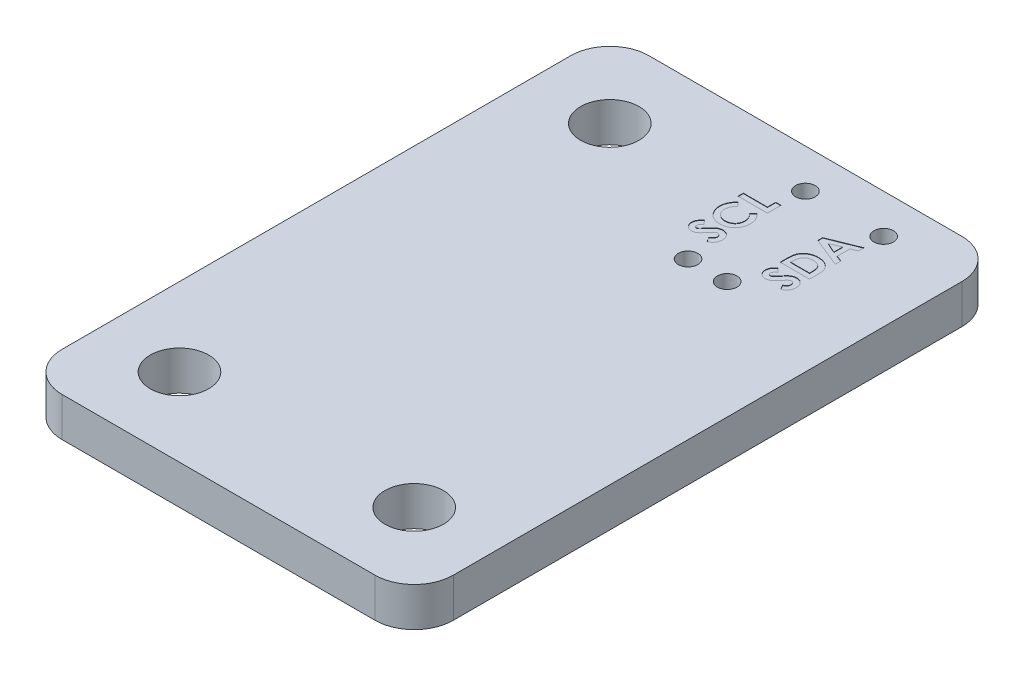
SolidWorks part; units mm, degrees
ref_plane "Front Plane" through (0, 0, 0) normal (0, 0, 1) x (1, 0, 0)
ref_plane "Top Plane" through (0, 0, 0) normal (0, 1, 0) x (1, 0, 0)
ref_plane "Right Plane" through (0, 0, 0) normal (1, 0, 0) x (0, 0, -1)
sketch "Sketch1" plane through (0, 0, 0) normal (0, 1, 0) x (1, 0, 0)
  line L1 (-12.7, -19.05) -> (12.7, -19.05)
  line L2 (-12.7, -19.05) -> (-12.7, 19.05)
  line L3 (-12.7, 19.05) -> (12.7, 19.05)
  line L4 (12.7, -19.05) -> (12.7, 19.05)
  line L5 (-12.7, -19.05) -> (12.7, 19.05) construction
  line L6 (-12.7, 19.05) -> (12.7, -19.05) construction
  point P0 (0, 0)
  dimension "D1" = 38.1
  dimension "D2" = 25.4
extrude "Boss-Extrude1" add sketch "Sketch1" along normal mid plane 2.54
fillet "Fillet1" radius 2.54 4 edges at (-12.7, 0, -19.05) (12.7, 0, -19.05) (-12.7, 0, 19.05) (12.7, 0, 19.05)
sketch "Sketch2" plane through (0, 1.27, 0) normal (0, 1, 0) x (1, 0, 0)
  line L0 (12.7, -16.51) -> (12.7, 16.51) construction
  line L1 (10.16, 19.05) -> (-10.16, 19.05) construction
  line L2 (2.54, 16.51) -> (2.54, 8.89) construction
  line L3 (7.62, 16.51) -> (7.62, 8.89) construction
  circle A0 centre (7.62, 16.51) radius 0.635
  circle A1 centre (2.54, 16.51) radius 0.635
  circle A2 centre (5.08, 8.89) radius 0.635
  circle A3 centre (2.54, 8.89) radius 0.635
  dimension "D6" = 1.27
  dimension "D1" = 5.08
  dimension "D2" = 5.08
  dimension "D3" = 2.54
  dimension "D4" = 2.54
  dimension "D5" = 7.62
  dimension "D7" = 7.62
  dimension "D8" = 10.16
extrude "Cut-Extrude1" cut sketch "Sketch2" against normal through all
sketch "Sketch4" plane through (0, 1.27, 0) normal (0, 1, 0) x (1, 0, 0)
  text T0 "<b>SCL</b>" font "Century Gothic" height 1.905
  text T1 "<b>SDA</b>" font "Century Gothic" height 1.905
extrude "Cut-Extrude2" cut sketch "Sketch4" against normal blind 0.0254
sketch "Sketch5" plane through (0, 1.27, 0) normal (0, 1, 0) x (1, 0, 0)
  line L1 (-12.7, 16.51) -> (-12.7, -16.51) construction
  line L2 (10.16, 19.05) -> (-10.16, 19.05) construction
  line L3 (-10.16, -19.05) -> (10.16, -19.05) construction
  line L4 (12.7, -16.51) -> (12.7, 16.51) construction
  circle A0 centre (-7.62, 13.97) radius 1.905
  circle A1 centre (-7.62, -13.97) radius 1.905
  circle A2 centre (7.62, -13.97) radius 1.905
  point P0 (-7.62, 13.97)
  point P2 (-7.62, -13.97)
  point P4 (7.62, -13.97)
  dimension "D1" = 3.81
  dimension "D2" = 5.08
  dimension "D3" = 5.08
  dimension "D4" = 5.08
  dimension "D5" = 5.08
  dimension "D6" = 5.08
hole_wizard "#6 Clearance Hole1" positions "Sketch5" profile "Sketch6" hole size "#6" standard "ANSI Inch" end condition through all
sketch "Sketch6" plane through (-7.62, 1.27, -13.97) normal (1, 0, 0) x (0, 0, 1)
  line L0 (0, 0) -> (0, 2.54)
  line L1 (0, 2.54) -> (1.8986, 2.54)
  line L2 (1.8986, 2.54) -> (1.8986, 0)
  line L5 (1.8986, 0) -> (0, 0)
  line L11 (0, -6.35) -> (0, 107.95) construction
  dimension "Thru Hole Dia." = 3.7973
  dimension "Thru Hole Depth" = 2.54
